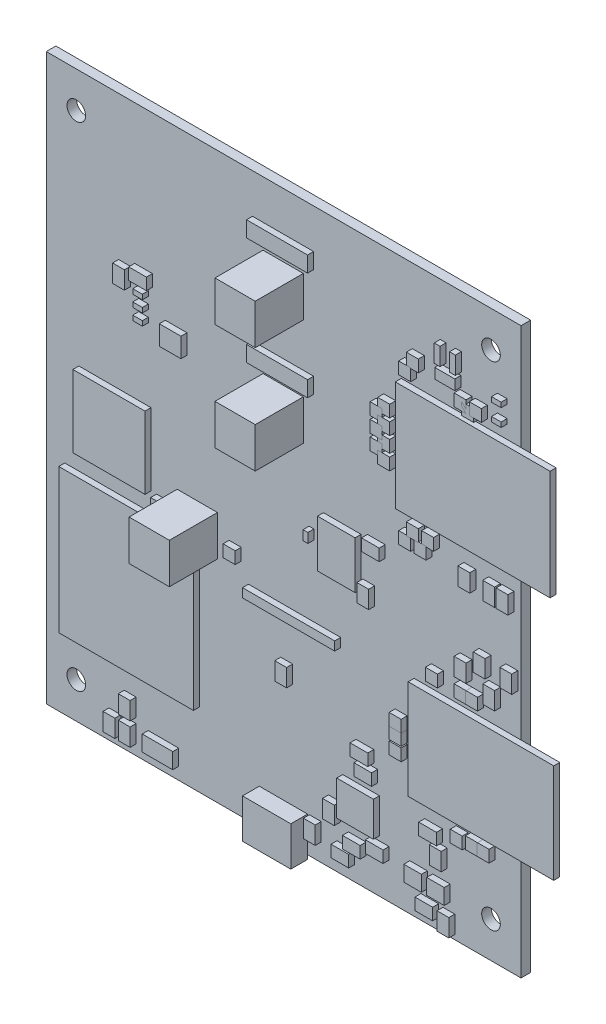
SolidWorks part; units mm, degrees
ref_plane "Front Plane" through (0, 0, 0) normal (0, 0, 1) x (1, 0, 0)
ref_plane "Top Plane" through (0, 0, 0) normal (0, 1, 0) x (1, 0, 0)
ref_plane "Right Plane" through (0, 0, 0) normal (1, 0, 0) x (0, 0, -1)
sketch "Sketch1" plane through (0, 0, 0) normal (0, 0, 1) x (1, 0, 0)
  line L0 (0, 0) -> (79, 0)
  line L1 (79, 0) -> (79, 94)
  line L2 (79, 94) -> (0, 94)
  line L3 (0, 94) -> (0, 0)
extrude "BOARD" add sketch "Sketch1" along normal blind 1.6 separate body
ref_plane "Plane1" through (0, 0, 1.6) normal (0, 0, 1) x (1, 0, 0)
sketch "Sketch2" plane through (0, 0, 1.6) normal (0, 0, 1) x (1, 0, 0)
  line L0 (25.4896, 36.2575) -> (25.4895, 12.2959)
  line L1 (25.4895, 12.2959) -> (3.0854, 12.2959)
  line L2 (3.0854, 12.2959) -> (3.0855, 36.2575)
  line L3 (3.0855, 36.2575) -> (25.4896, 36.2575)
extrude "BATTCOM_20MM_PTH_KIT-1" add sketch "Sketch2" along normal blind 1 separate body
sketch "Sketch3" plane through (0, 0, 0) normal (0, 0, 1) x (1, 0, 0)
  line L0 (38.9, 43.5808) -> (37.3, 43.5808)
  line L1 (37.3, 43.5808) -> (37.3, 42.78)
  line L2 (37.3, 42.78) -> (38.9, 42.78)
  line L3 (38.9, 42.78) -> (38.9, 43.5808)
extrude "C0603K-1" add sketch "Sketch3" against normal blind 1 separate body
sketch "Sketch4" plane through (0, 0, 0) normal (0, 0, 1) x (1, 0, 0)
  line L0 (35.3258, 23.965) -> (35.3258, 25.565)
  line L1 (35.3258, 25.565) -> (34.525, 25.565)
  line L2 (34.525, 25.565) -> (34.525, 23.965)
  line L3 (34.525, 23.965) -> (35.3258, 23.965)
extrude "C0603K-2" add sketch "Sketch4" against normal blind 1 separate body
sketch "Sketch5" plane through (0, 0, 0) normal (0, 0, 1) x (1, 0, 0)
  line L0 (37.5483, 23.965) -> (37.5483, 25.565)
  line L1 (37.5483, 25.565) -> (36.7475, 25.565)
  line L2 (36.7475, 25.565) -> (36.7475, 23.965)
  line L3 (36.7475, 23.965) -> (37.5483, 23.965)
extrude "C0603K-3" add sketch "Sketch5" against normal blind 1 separate body
sketch "Sketch6" plane through (0, 0, 0) normal (0, 0, 1) x (1, 0, 0)
  line L0 (40.0883, 23.965) -> (40.0883, 25.565)
  line L1 (40.0883, 25.565) -> (39.2875, 25.565)
  line L2 (39.2875, 25.565) -> (39.2875, 23.965)
  line L3 (39.2875, 23.965) -> (40.0883, 23.965)
extrude "C0603K-4" add sketch "Sketch6" against normal blind 1 separate body
sketch "Sketch7" plane through (0, 0, 0) normal (0, 0, 1) x (1, 0, 0)
  line L0 (42.3108, 23.965) -> (42.3108, 25.565)
  line L1 (42.3108, 25.565) -> (41.51, 25.565)
  line L2 (41.51, 25.565) -> (41.51, 23.965)
  line L3 (41.51, 23.965) -> (42.3108, 23.965)
extrude "C0603K-5" add sketch "Sketch7" against normal blind 1 separate body
sketch "Sketch8" plane through (0, 0, 0) normal (0, 0, 1) x (1, 0, 0)
  line L0 (38.57, 88.4992) -> (40.17, 88.4992)
  line L1 (40.17, 88.4992) -> (40.17, 89.3)
  line L2 (40.17, 89.3) -> (38.57, 89.3)
  line L3 (38.57, 89.3) -> (38.57, 88.4992)
extrude "C0603K-6" add sketch "Sketch8" against normal blind 1 separate body
sketch "Sketch9" plane through (0, 0, 0) normal (0, 0, 1) x (1, 0, 0)
  line L0 (28.423, 9.0045) -> (28.423, 11.9505)
  line L1 (28.423, 11.9505) -> (27.457, 11.9505)
  line L2 (27.457, 11.9505) -> (27.457, 9.0045)
  line L3 (27.457, 9.0045) -> (28.423, 9.0045)
extrude "C0402-1" add sketch "Sketch9" against normal blind 1 separate body
sketch "Sketch10" plane through (0, 0, 0) normal (0, 0, 1) x (1, 0, 0)
  line L0 (27.457, 20.2055) -> (27.457, 17.2595)
  line L1 (27.457, 17.2595) -> (28.423, 17.2595)
  line L2 (28.423, 17.2595) -> (28.423, 20.2055)
  line L3 (28.423, 20.2055) -> (27.457, 20.2055)
extrude "C0402-2" add sketch "Sketch10" against normal blind 1 separate body
sketch "Sketch11" plane through (0, 0, 0) normal (0, 0, 1) x (1, 0, 0)
  line L0 (38.57, 71.0367) -> (40.17, 71.0367)
  line L1 (40.17, 71.0367) -> (40.17, 71.8375)
  line L2 (40.17, 71.8375) -> (38.57, 71.8375)
  line L3 (38.57, 71.8375) -> (38.57, 71.0367)
extrude "C0603K-7" add sketch "Sketch11" against normal blind 1 separate body
sketch "Sketch12" plane through (0, 0, 0) normal (0, 0, 1) x (1, 0, 0)
  line L0 (18.9667, 23.3425) -> (18.9667, 21.7425)
  line L1 (18.9667, 21.7425) -> (19.7675, 21.7425)
  line L2 (19.7675, 21.7425) -> (19.7675, 23.3425)
  line L3 (19.7675, 23.3425) -> (18.9667, 23.3425)
extrude "C0603K-8" add sketch "Sketch12" against normal blind 1 separate body
sketch "Sketch13" plane through (0, 0, 0) normal (0, 0, 1) x (1, 0, 0)
  line L0 (65.0042, 30.3275) -> (65.0042, 28.7275)
  line L1 (65.0042, 28.7275) -> (65.805, 28.7275)
  line L2 (65.805, 28.7275) -> (65.805, 30.3275)
  line L3 (65.805, 30.3275) -> (65.0042, 30.3275)
extrude "C0603K-9" add sketch "Sketch13" against normal blind 1 separate body
sketch "Sketch14" plane through (0, 0, 0) normal (0, 0, 1) x (1, 0, 0)
  line L0 (66.9092, 30.3275) -> (66.9092, 28.7275)
  line L1 (66.9092, 28.7275) -> (67.71, 28.7275)
  line L2 (67.71, 28.7275) -> (67.71, 30.3275)
  line L3 (67.71, 30.3275) -> (66.9092, 30.3275)
extrude "C0603K-10" add sketch "Sketch14" against normal blind 1 separate body
sketch "Sketch15" plane through (0, 0, 0) normal (0, 0, 1) x (1, 0, 0)
  line L0 (43.3325, 12.9342) -> (44.9325, 12.9342)
  line L1 (44.9325, 12.9342) -> (44.9325, 13.735)
  line L2 (44.9325, 13.735) -> (43.3325, 13.735)
  line L3 (43.3325, 13.735) -> (43.3325, 12.9342)
extrude "C0603K-11" add sketch "Sketch15" against normal blind 1 separate body
sketch "Sketch16" plane through (0, 0, 1.6) normal (0, 0, 1) x (1, 0, 0)
  line L0 (42.7716, 58.93) -> (36.07, 58.93)
  line L1 (36.07, 58.93) -> (36.07, 65.6316)
  line L2 (36.07, 65.6316) -> (42.7716, 65.6316)
  line L3 (42.7716, 65.6316) -> (42.7716, 58.93)
extrude "153CLV-0605-1" add sketch "Sketch16" along normal blind 8 separate body
sketch "Sketch17" plane through (0, 0, 1.6) normal (0, 0, 1) x (1, 0, 0)
  line L0 (42.7716, 76.71) -> (36.07, 76.71)
  line L1 (36.07, 76.71) -> (36.07, 83.4116)
  line L2 (36.07, 83.4116) -> (42.7716, 83.4116)
  line L3 (42.7716, 83.4116) -> (42.7716, 76.71)
extrude "153CLV-0605-2" add sketch "Sketch17" along normal blind 8 separate body
sketch "Sketch18" plane through (0, 0, 0) normal (0, 0, 1) x (1, 0, 0)
  line L0 (67.7925, 22.3083) -> (66.1925, 22.3083)
  line L1 (66.1925, 22.3083) -> (66.1925, 21.5075)
  line L2 (66.1925, 21.5075) -> (67.7925, 21.5075)
  line L3 (67.7925, 21.5075) -> (67.7925, 22.3083)
extrude "C0603K-12" add sketch "Sketch18" against normal blind 1 separate body
sketch "Sketch19" plane through (0, 0, 1.6) normal (0, 0, 1) x (1, 0, 0)
  line L0 (43.7317, 45.8725) -> (43.7317, 47.4725)
  line L1 (43.7317, 47.4725) -> (44.5325, 47.4725)
  line L2 (44.5325, 47.4725) -> (44.5325, 45.8725)
  line L3 (44.5325, 45.8725) -> (43.7317, 45.8725)
extrude "C0603K-13" add sketch "Sketch19" along normal blind 1 separate body
sketch "Sketch20" plane through (0, 0, 0) normal (0, 0, 1) x (1, 0, 0)
  line L0 (6.1158, 54.445) -> (6.1158, 56.045)
  line L1 (6.1158, 56.045) -> (5.315, 56.045)
  line L2 (5.315, 56.045) -> (5.315, 54.445)
  line L3 (5.315, 54.445) -> (6.1158, 54.445)
extrude "C0603K-14" add sketch "Sketch20" against normal blind 1 separate body
sketch "Sketch21" plane through (0, 0, 0) normal (0, 0, 1) x (1, 0, 0)
  line L0 (7.785, 58.5033) -> (6.185, 58.5033)
  line L1 (6.185, 58.5033) -> (6.185, 57.7025)
  line L2 (6.185, 57.7025) -> (7.785, 57.7025)
  line L3 (7.785, 57.7025) -> (7.785, 58.5033)
extrude "C0603K-15" add sketch "Sketch21" against normal blind 1 separate body
sketch "Sketch22" plane through (0, 0, 0) normal (0, 0, 1) x (1, 0, 0)
  line L0 (15.0058, 52.54) -> (15.0058, 54.14)
  line L1 (15.0058, 54.14) -> (14.205, 54.14)
  line L2 (14.205, 54.14) -> (14.205, 52.54)
  line L3 (14.205, 52.54) -> (15.0058, 52.54)
extrude "C0603K-16" add sketch "Sketch22" against normal blind 1 separate body
sketch "Sketch23" plane through (0, 0, 0) normal (0, 0, 1) x (1, 0, 0)
  line L0 (24.2825, 39.2867) -> (25.8825, 39.2867)
  line L1 (25.8825, 39.2867) -> (25.8825, 40.0875)
  line L2 (25.8825, 40.0875) -> (24.2825, 40.0875)
  line L3 (24.2825, 40.0875) -> (24.2825, 39.2867)
extrude "C0603K-17" add sketch "Sketch23" against normal blind 1 separate body
sketch "Sketch24" plane through (0, 0, 0) normal (0, 0, 1) x (1, 0, 0)
  line L0 (27.8567, 43.0275) -> (27.8567, 41.4275)
  line L1 (27.8567, 41.4275) -> (28.6575, 41.4275)
  line L2 (28.6575, 41.4275) -> (28.6575, 43.0275)
  line L3 (28.6575, 43.0275) -> (27.8567, 43.0275)
extrude "C0603K-18" add sketch "Sketch24" against normal blind 1 separate body
sketch "Sketch25" plane through (0, 0, 1.6) normal (0, 0, 1) x (1, 0, 0)
  line L0 (28.4841, 35.1175) -> (21.7825, 35.1175)
  line L1 (21.7825, 35.1175) -> (21.7825, 41.8191)
  line L2 (21.7825, 41.8191) -> (28.4841, 41.8191)
  line L3 (28.4841, 41.8191) -> (28.4841, 35.1175)
extrude "153CLV-0605-3" add sketch "Sketch25" along normal blind 8 separate body
sketch "Sketch26" plane through (0, 0, 1.6) normal (0, 0, 1) x (1, 0, 0)
  line L0 (75.0825, 79.4583) -> (76.6825, 79.4583)
  line L1 (76.6825, 79.4583) -> (76.6825, 78.6575)
  line L2 (76.6825, 78.6575) -> (75.0825, 78.6575)
  line L3 (75.0825, 78.6575) -> (75.0825, 79.4583)
extrude "C0603K-19" add sketch "Sketch26" along normal blind 1 separate body
sketch "Sketch27" plane through (0, 0, 1.6) normal (0, 0, 1) x (1, 0, 0)
  line L0 (75.0825, 82.3158) -> (76.6825, 82.3158)
  line L1 (76.6825, 82.3158) -> (76.6825, 81.515)
  line L2 (76.6825, 81.515) -> (75.0825, 81.515)
  line L3 (75.0825, 81.515) -> (75.0825, 82.3158)
extrude "C0603K-20" add sketch "Sketch27" along normal blind 1 separate body
sketch "Sketch28" plane through (0, 0, 1.6) normal (0, 0, 1) x (1, 0, 0)
  line L0 (16.9925, 63.4167) -> (15.3925, 63.4167)
  line L1 (15.3925, 63.4167) -> (15.3925, 64.2175)
  line L2 (15.3925, 64.2175) -> (16.9925, 64.2175)
  line L3 (16.9925, 64.2175) -> (16.9925, 63.4167)
extrude "C0603K-21" add sketch "Sketch28" along normal blind 1 separate body
sketch "Sketch29" plane through (0, 0, 1.6) normal (0, 0, 1) x (1, 0, 0)
  line L0 (16.9925, 65.3217) -> (15.3925, 65.3217)
  line L1 (15.3925, 65.3217) -> (15.3925, 66.1225)
  line L2 (15.3925, 66.1225) -> (16.9925, 66.1225)
  line L3 (16.9925, 66.1225) -> (16.9925, 65.3217)
extrude "C0603K-22" add sketch "Sketch29" along normal blind 1 separate body
sketch "Sketch30" plane through (0, 0, 1.6) normal (0, 0, 1) x (1, 0, 0)
  line L0 (16.9925, 67.2267) -> (15.3925, 67.2267)
  line L1 (15.3925, 67.2267) -> (15.3925, 68.0275)
  line L2 (15.3925, 68.0275) -> (16.9925, 68.0275)
  line L3 (16.9925, 68.0275) -> (16.9925, 67.2267)
extrude "C0603K-23" add sketch "Sketch30" along normal blind 1 separate body
sketch "Sketch31" plane through (0, 0, 1.6) normal (0, 0, 1) x (1, 0, 0)
  line L0 (65.557, 82.347) -> (65.557, 85.293)
  line L1 (65.557, 85.293) -> (66.523, 85.293)
  line L2 (66.523, 85.293) -> (66.523, 82.347)
  line L3 (66.523, 82.347) -> (65.557, 82.347)
extrude "C0402-3" add sketch "Sketch31" along normal blind 1 separate body
sketch "Sketch32" plane through (0, 0, 1.6) normal (0, 0, 1) x (1, 0, 0)
  line L0 (68.097, 82.347) -> (68.097, 85.293)
  line L1 (68.097, 85.293) -> (69.063, 85.293)
  line L2 (69.063, 85.293) -> (69.063, 82.347)
  line L3 (69.063, 82.347) -> (68.097, 82.347)
extrude "C0402-4" add sketch "Sketch32" along normal blind 1 separate body
sketch "Sketch33" plane through (0, 0, 0) normal (0, 0, 1) x (1, 0, 0)
  line L0 (66.4408, 24.2825) -> (66.4408, 25.8825)
  line L1 (66.4408, 25.8825) -> (65.64, 25.8825)
  line L2 (65.64, 25.8825) -> (65.64, 24.2825)
  line L3 (65.64, 24.2825) -> (66.4408, 24.2825)
extrude "C0603K-24" add sketch "Sketch33" against normal blind 1 separate body
sketch "Sketch34" plane through (0, 0, 0) normal (0, 0, 1) x (1, 0, 0)
  line L0 (42.4307, 50.0507) -> (36.8065, 50.0507)
  line L1 (36.8065, 50.0507) -> (36.8065, 44.3738)
  line L2 (36.8065, 44.3738) -> (42.4307, 44.3738)
  line L3 (42.4307, 44.3738) -> (42.4307, 50.0507)
extrude "WS2812B-1" add sketch "Sketch34" against normal blind 1 separate body
sketch "Sketch35" plane through (0, 0, 0) normal (0, 0, 1) x (1, 0, 0)
  line L0 (40.7924, 41.6179) -> (37.8714, 41.6179)
  line L1 (37.8714, 41.6179) -> (37.8714, 39.0271)
  line L2 (37.8714, 39.0271) -> (40.7924, 39.0271)
  line L3 (40.7924, 39.0271) -> (40.7924, 41.6179)
extrude "SOT23-1" add sketch "Sketch35" against normal blind 1 separate body
sketch "Sketch36" plane through (0, 0, 0) normal (0, 0, 1) x (1, 0, 0)
  line L0 (45.5676, 21.5646) -> (48.4886, 21.5646)
  line L1 (48.4886, 21.5646) -> (48.4886, 24.1554)
  line L2 (48.4886, 24.1554) -> (45.5676, 24.1554)
  line L3 (45.5676, 24.1554) -> (45.5676, 21.5646)
extrude "SOT23-2" add sketch "Sketch36" against normal blind 1 separate body
sketch "Sketch37" plane through (0, 0, 1.6) normal (0, 0, 1) x (1, 0, 0)
  line L0 (49.3332, 14.4843) -> (55.4375, 14.4843)
  line L1 (55.4375, 14.4843) -> (55.4375, 8.705)
  line L2 (55.4375, 8.705) -> (49.3332, 8.705)
  line L3 (49.3332, 8.705) -> (49.3332, 14.4843)
extrude "MLP28-1" add sketch "Sketch37" along normal blind 1 separate body
sketch "Sketch38" plane through (0, 0, 0) normal (0, 0, 1) x (1, 0, 0)
  line L0 (12.53, 52.1384) -> (12.53, 54.5416)
  line L1 (12.53, 54.5416) -> (10.33, 54.5416)
  line L2 (10.33, 54.5416) -> (10.33, 52.1384)
  line L3 (10.33, 52.1384) -> (12.53, 52.1384)
extrude "SC70-5L-1" add sketch "Sketch38" against normal blind 1 separate body
sketch "Sketch39" plane through (0, 0, 1.6) normal (0, 0, 1) x (1, 0, 0)
  line L0 (48.9966, 32.6009) -> (33.655, 32.6009)
  line L1 (33.655, 32.6009) -> (33.655, 34.0741)
  line L2 (33.655, 34.0741) -> (48.9966, 34.0741)
  line L3 (48.9966, 34.0741) -> (48.9966, 32.6009)
extrude "1X06_LONGPADS-1" add sketch "Sketch39" along normal blind 1 separate body
sketch "Sketch40" plane through (0, 0, 1.6) normal (0, 0, 1) x (1, 0, 0)
  line L0 (35.4484, 5.8633) -> (43.4884, 5.8633)
  line L1 (43.4884, 5.8633) -> (43.4884, -0.6707)
  line L2 (43.4884, -0.6707) -> (35.4484, -0.6707)
  line L3 (35.4484, -0.6707) -> (35.4484, 5.8633)
extrude "USB-MICROB-PTH-MILL-1" add sketch "Sketch40" along normal blind 2.8 separate body
sketch "Sketch41" plane through (0, 0, 0) normal (0, 0, 1) x (1, 0, 0)
  line L0 (19.1291, 44.7259) -> (19.1291, 39.7291)
  line L1 (19.1291, 39.7291) -> (22.1205, 39.7291)
  line L2 (22.1205, 39.7291) -> (22.1205, 44.7259)
  line L3 (22.1205, 44.7259) -> (19.1291, 44.7259)
extrude "L3225M-1" add sketch "Sketch41" against normal blind 1 separate body
sketch "Sketch42" plane through (0, 0, 1.6) normal (0, 0, 1) x (1, 0, 0)
  line L0 (34.3237, 69.4585) -> (44.4837, 69.4585)
  line L1 (44.4837, 69.4585) -> (44.4837, 66.8423)
  line L2 (44.4837, 66.8423) -> (34.3237, 66.8423)
  line L3 (34.3237, 66.8423) -> (34.3237, 69.4585)
extrude "1X04-1" add sketch "Sketch42" along normal blind 1 separate body
sketch "Sketch43" plane through (0, 0, 1.6) normal (0, 0, 1) x (1, 0, 0)
  line L0 (34.3232, 87.4253) -> (44.4832, 87.4253)
  line L1 (44.4832, 87.4253) -> (44.4832, 84.8091)
  line L2 (44.4832, 84.8091) -> (34.3232, 84.8091)
  line L3 (34.3232, 84.8091) -> (34.3232, 87.4253)
extrude "1X04-2" add sketch "Sketch43" along normal blind 1 separate body
sketch "Sketch44" plane through (0, 0, 1.6) normal (0, 0, 1) x (1, 0, 0)
  line L0 (16.9625, 4.6457) -> (22.0425, 4.6457)
  line L1 (22.0425, 4.6457) -> (22.0425, 2.0295)
  line L2 (22.0425, 2.0295) -> (16.9625, 2.0295)
  line L3 (16.9625, 2.0295) -> (16.9625, 4.6457)
extrude "1X02-1" add sketch "Sketch44" along normal blind 1 separate body
sketch "Sketch45" plane through (0, 0, 1.6) normal (0, 0, 1) x (1, 0, 0)
  line L0 (5.4284, 51.4041) -> (17.4316, 51.4041)
  line L1 (17.4316, 51.4041) -> (17.4316, 39.4009)
  line L2 (17.4316, 39.4009) -> (5.4284, 39.4009)
  line L3 (5.4284, 39.4009) -> (5.4284, 51.4041)
extrude "BUZZER-12MM-NS-KIT-1" add sketch "Sketch45" along normal blind 1 separate body
sketch "Sketch46" plane through (0, 0, 1.6) normal (0, 0, 1) x (1, 0, 0)
  line L0 (66.0095, 0.7495) -> (66.0095, 3.6955)
  line L1 (66.0095, 3.6955) -> (67.9755, 3.6955)
  line L2 (67.9755, 3.6955) -> (67.9755, 0.7495)
  line L3 (67.9755, 0.7495) -> (66.0095, 0.7495)
extrude "R0603-1" add sketch "Sketch46" along normal blind 1 separate body
sketch "Sketch47" plane through (0, 0, 1.6) normal (0, 0, 1) x (1, 0, 0)
  line L0 (65.2905, 1.8745) -> (62.3445, 1.8745)
  line L1 (62.3445, 1.8745) -> (62.3445, 3.8405)
  line L2 (62.3445, 3.8405) -> (65.2905, 3.8405)
  line L3 (65.2905, 3.8405) -> (65.2905, 1.8745)
extrude "R0603-2" add sketch "Sketch47" along normal blind 1 separate body
sketch "Sketch48" plane through (0, 0, 1.6) normal (0, 0, 1) x (1, 0, 0)
  line L0 (54.4955, 18.702) -> (51.5495, 18.702)
  line L1 (51.5495, 18.702) -> (51.5495, 20.668)
  line L2 (51.5495, 20.668) -> (54.4955, 20.668)
  line L3 (54.4955, 20.668) -> (54.4955, 18.702)
extrude "R0603-3" add sketch "Sketch48" along normal blind 1 separate body
sketch "Sketch49" plane through (0, 0, 1.6) normal (0, 0, 1) x (1, 0, 0)
  line L0 (55.1305, 16.162) -> (52.1845, 16.162)
  line L1 (52.1845, 16.162) -> (52.1845, 18.128)
  line L2 (52.1845, 18.128) -> (55.1305, 18.128)
  line L3 (55.1305, 18.128) -> (55.1305, 16.162)
extrude "R0603-4" add sketch "Sketch49" along normal blind 1 separate body
sketch "Sketch50" plane through (0, 0, 0) normal (0, 0, 1) x (1, 0, 0)
  line L0 (39.802, 10.447) -> (42.748, 10.447)
  line L1 (42.748, 10.447) -> (42.748, 12.413)
  line L2 (42.748, 12.413) -> (39.802, 12.413)
  line L3 (39.802, 12.413) -> (39.802, 10.447)
extrude "R0603-5" add sketch "Sketch50" against normal blind 1 separate body
sketch "Sketch51" plane through (0, 0, 0) normal (0, 0, 1) x (1, 0, 0)
  line L0 (38.6205, 12.413) -> (35.6745, 12.413)
  line L1 (35.6745, 12.413) -> (35.6745, 10.447)
  line L2 (35.6745, 10.447) -> (38.6205, 10.447)
  line L3 (38.6205, 10.447) -> (38.6205, 12.413)
extrude "R0603-6" add sketch "Sketch51" against normal blind 1 separate body
sketch "Sketch52" plane through (0, 0, 0) normal (0, 0, 1) x (1, 0, 0)
  line L0 (46.4695, 16.162) -> (49.4155, 16.162)
  line L1 (49.4155, 16.162) -> (49.4155, 18.128)
  line L2 (49.4155, 18.128) -> (46.4695, 18.128)
  line L3 (46.4695, 18.128) -> (46.4695, 16.162)
extrude "R0603-7" add sketch "Sketch52" against normal blind 1 separate body
sketch "Sketch53" plane through (0, 0, 0) normal (0, 0, 1) x (1, 0, 0)
  line L0 (41.3055, 10.9095) -> (41.3055, 13.8555)
  line L1 (41.3055, 13.8555) -> (39.3395, 13.8555)
  line L2 (39.3395, 13.8555) -> (39.3395, 10.9095)
  line L3 (39.3395, 10.9095) -> (41.3055, 10.9095)
extrude "R0603-8" add sketch "Sketch53" against normal blind 1 separate body
sketch "Sketch54" plane through (0, 0, 0) normal (0, 0, 1) x (1, 0, 0)
  line L0 (39.083, 10.9095) -> (39.083, 13.8555)
  line L1 (39.083, 13.8555) -> (37.117, 13.8555)
  line L2 (37.117, 13.8555) -> (37.117, 10.9095)
  line L3 (37.117, 10.9095) -> (39.083, 10.9095)
extrude "R0603-9" add sketch "Sketch54" against normal blind 1 separate body
sketch "Sketch55" plane through (0, 0, 0) normal (0, 0, 1) x (1, 0, 0)
  line L0 (46.4695, 18.702) -> (49.4155, 18.702)
  line L1 (49.4155, 18.702) -> (49.4155, 20.668)
  line L2 (49.4155, 20.668) -> (46.4695, 20.668)
  line L3 (46.4695, 20.668) -> (46.4695, 18.702)
extrude "R0603-10" add sketch "Sketch55" against normal blind 1 separate body
sketch "Sketch56" plane through (0, 0, 1.6) normal (0, 0, 1) x (1, 0, 0)
  line L0 (40.988, 26.238) -> (40.988, 23.292)
  line L1 (40.988, 23.292) -> (39.022, 23.292)
  line L2 (39.022, 23.292) -> (39.022, 26.238)
  line L3 (39.022, 26.238) -> (40.988, 26.238)
extrude "R0603-11" add sketch "Sketch56" along normal blind 1 separate body
sketch "Sketch57" plane through (0, 0, 0) normal (0, 0, 1) x (1, 0, 0)
  line L0 (77.818, 21.387) -> (77.818, 24.333)
  line L1 (77.818, 24.333) -> (75.852, 24.333)
  line L2 (75.852, 24.333) -> (75.852, 21.387)
  line L3 (75.852, 21.387) -> (77.818, 21.387)
extrude "R0603-12" add sketch "Sketch57" against normal blind 1 separate body
sketch "Sketch58" plane through (0, 0, 0) normal (0, 0, 1) x (1, 0, 0)
  line L0 (75.278, 21.387) -> (75.278, 24.333)
  line L1 (75.278, 24.333) -> (73.312, 24.333)
  line L2 (73.312, 24.333) -> (73.312, 21.387)
  line L3 (73.312, 21.387) -> (75.278, 21.387)
extrude "R0603-13" add sketch "Sketch58" against normal blind 1 separate body
sketch "Sketch59" plane through (0, 0, 1.6) normal (0, 0, 1) x (1, 0, 0)
  line L0 (75.5955, 40.208) -> (75.5955, 37.262)
  line L1 (75.5955, 37.262) -> (73.6295, 37.262)
  line L2 (73.6295, 37.262) -> (73.6295, 40.208)
  line L3 (73.6295, 40.208) -> (75.5955, 40.208)
extrude "R0603-14" add sketch "Sketch59" along normal blind 1 separate body
sketch "Sketch60" plane through (0, 0, 0) normal (0, 0, 1) x (1, 0, 0)
  line L0 (69.2455, 23.6095) -> (69.2455, 26.5555)
  line L1 (69.2455, 26.5555) -> (67.2795, 26.5555)
  line L2 (67.2795, 26.5555) -> (67.2795, 23.6095)
  line L3 (67.2795, 23.6095) -> (69.2455, 23.6095)
extrude "R0603-15" add sketch "Sketch60" against normal blind 1 separate body
sketch "Sketch61" plane through (0, 0, 0) normal (0, 0, 1) x (1, 0, 0)
  line L0 (14.7195, 27.2745) -> (17.6655, 27.2745)
  line L1 (17.6655, 27.2745) -> (17.6655, 29.2405)
  line L2 (17.6655, 29.2405) -> (14.7195, 29.2405)
  line L3 (14.7195, 29.2405) -> (14.7195, 27.2745)
extrude "R0603-16" add sketch "Sketch61" against normal blind 1 separate body
sketch "Sketch62" plane through (0, 0, 1.6) normal (0, 0, 1) x (1, 0, 0)
  line L0 (56.4005, 49.182) -> (53.4545, 49.182)
  line L1 (53.4545, 49.182) -> (53.4545, 51.148)
  line L2 (53.4545, 51.148) -> (56.4005, 51.148)
  line L3 (56.4005, 51.148) -> (56.4005, 49.182)
extrude "R0603-17" add sketch "Sketch62" along normal blind 1 separate body
sketch "Sketch63" plane through (0, 0, 1.6) normal (0, 0, 1) x (1, 0, 0)
  line L0 (12.413, 4.648) -> (12.413, 1.702)
  line L1 (12.413, 1.702) -> (10.447, 1.702)
  line L2 (10.447, 1.702) -> (10.447, 4.648)
  line L3 (10.447, 4.648) -> (12.413, 4.648)
extrude "R0603-18" add sketch "Sketch63" along normal blind 1 separate body
sketch "Sketch64" plane through (0, 0, 1.6) normal (0, 0, 1) x (1, 0, 0)
  line L0 (14.953, 8.458) -> (14.953, 5.512)
  line L1 (14.953, 5.512) -> (12.987, 5.512)
  line L2 (12.987, 5.512) -> (12.987, 8.458)
  line L3 (12.987, 8.458) -> (14.953, 8.458)
extrude "R0603-19" add sketch "Sketch64" along normal blind 1 separate body
sketch "Sketch65" plane through (0, 0, 1.6) normal (0, 0, 1) x (1, 0, 0)
  line L0 (14.953, 4.648) -> (14.953, 1.702)
  line L1 (14.953, 1.702) -> (12.987, 1.702)
  line L2 (12.987, 1.702) -> (12.987, 4.648)
  line L3 (12.987, 4.648) -> (14.953, 4.648)
extrude "R0603-20" add sketch "Sketch65" along normal blind 1 separate body
sketch "Sketch66" plane through (0, 0, 1.6) normal (0, 0, 1) x (1, 0, 0)
  line L0 (45.7505, 5.918) -> (45.7505, 2.972)
  line L1 (45.7505, 2.972) -> (43.7845, 2.972)
  line L2 (43.7845, 2.972) -> (43.7845, 5.918)
  line L3 (43.7845, 5.918) -> (45.7505, 5.918)
extrude "R0603-21" add sketch "Sketch66" along normal blind 1 separate body
sketch "Sketch67" plane through (0, 0, 0) normal (0, 0, 1) x (1, 0, 0)
  line L0 (37.4955, 38.532) -> (37.4955, 41.478)
  line L1 (37.4955, 41.478) -> (35.5295, 41.478)
  line L2 (35.5295, 41.478) -> (35.5295, 38.532)
  line L3 (35.5295, 38.532) -> (37.4955, 38.532)
extrude "R0603-22" add sketch "Sketch67" against normal blind 1 separate body
sketch "Sketch68" plane through (0, 0, 0) normal (0, 0, 1) x (1, 0, 0)
  line L0 (35.847, 53.2255) -> (35.847, 50.2795)
  line L1 (35.847, 50.2795) -> (37.813, 50.2795)
  line L2 (37.813, 50.2795) -> (37.813, 53.2255)
  line L3 (37.813, 53.2255) -> (35.847, 53.2255)
extrude "R0603-23" add sketch "Sketch68" against normal blind 1 separate body
sketch "Sketch69" plane through (0, 0, 0) normal (0, 0, 1) x (1, 0, 0)
  line L0 (40.353, 74.727) -> (40.353, 77.673)
  line L1 (40.353, 77.673) -> (38.387, 77.673)
  line L2 (38.387, 77.673) -> (38.387, 74.727)
  line L3 (38.387, 74.727) -> (40.353, 74.727)
extrude "R0603-24" add sketch "Sketch69" against normal blind 1 separate body
sketch "Sketch70" plane through (0, 0, 1.6) normal (0, 0, 1) x (1, 0, 0)
  line L0 (76.487, 41.072) -> (76.487, 44.018)
  line L1 (76.487, 44.018) -> (78.453, 44.018)
  line L2 (78.453, 44.018) -> (78.453, 41.072)
  line L3 (78.453, 41.072) -> (76.487, 41.072)
extrude "R0603-25" add sketch "Sketch70" along normal blind 1 separate body
sketch "Sketch71" plane through (0, 0, 1.6) normal (0, 0, 1) x (1, 0, 0)
  line L0 (72.042, 41.072) -> (72.042, 44.018)
  line L1 (72.042, 44.018) -> (74.008, 44.018)
  line L2 (74.008, 44.018) -> (74.008, 41.072)
  line L3 (74.008, 41.072) -> (72.042, 41.072)
extrude "R0603-26" add sketch "Sketch71" along normal blind 1 separate body
sketch "Sketch72" plane through (0, 0, 0) normal (0, 0, 1) x (1, 0, 0)
  line L0 (74.1805, 28.6055) -> (71.2345, 28.6055)
  line L1 (71.2345, 28.6055) -> (71.2345, 26.6395)
  line L2 (71.2345, 26.6395) -> (74.1805, 26.6395)
  line L3 (74.1805, 26.6395) -> (74.1805, 28.6055)
extrude "R0603-27" add sketch "Sketch72" against normal blind 1 separate body
sketch "Sketch73" plane through (0, 0, 0) normal (0, 0, 1) x (1, 0, 0)
  line L0 (66.7895, 32.037) -> (69.7355, 32.037)
  line L1 (69.7355, 32.037) -> (69.7355, 34.003)
  line L2 (69.7355, 34.003) -> (66.7895, 34.003)
  line L3 (66.7895, 34.003) -> (66.7895, 32.037)
extrude "R0603-28" add sketch "Sketch73" against normal blind 1 separate body
sketch "Sketch74" plane through (0, 0, 0) normal (0, 0, 1) x (1, 0, 0)
  line L0 (74.1805, 31.1455) -> (71.2345, 31.1455)
  line L1 (71.2345, 31.1455) -> (71.2345, 29.1795)
  line L2 (71.2345, 29.1795) -> (74.1805, 29.1795)
  line L3 (74.1805, 29.1795) -> (74.1805, 31.1455)
extrude "R0603-29" add sketch "Sketch74" against normal blind 1 separate body
sketch "Sketch75" plane through (0, 0, 1.6) normal (0, 0, 1) x (1, 0, 0)
  line L0 (65.9255, 12.987) -> (62.9795, 12.987)
  line L1 (62.9795, 12.987) -> (62.9795, 14.953)
  line L2 (62.9795, 14.953) -> (65.9255, 14.953)
  line L3 (65.9255, 14.953) -> (65.9255, 12.987)
extrude "R0603-30" add sketch "Sketch75" along normal blind 1 separate body
sketch "Sketch76" plane through (0, 0, 1.6) normal (0, 0, 1) x (1, 0, 0)
  line L0 (68.867, 38.8495) -> (68.867, 41.7955)
  line L1 (68.867, 41.7955) -> (70.833, 41.7955)
  line L2 (70.833, 41.7955) -> (70.833, 38.8495)
  line L3 (70.833, 38.8495) -> (68.867, 38.8495)
extrude "R0603-31" add sketch "Sketch76" along normal blind 1 separate body
sketch "Sketch77" plane through (0, 0, 0) normal (0, 0, 1) x (1, 0, 0)
  line L0 (12.497, 49.182) -> (15.443, 49.182)
  line L1 (15.443, 49.182) -> (15.443, 51.148)
  line L2 (15.443, 51.148) -> (12.497, 51.148)
  line L3 (12.497, 51.148) -> (12.497, 49.182)
extrude "R0603-32" add sketch "Sketch77" against normal blind 1 separate body
sketch "Sketch78" plane through (0, 0, 0) normal (0, 0, 1) x (1, 0, 0)
  line L0 (8.458, 61.6255) -> (5.512, 61.6255)
  line L1 (5.512, 61.6255) -> (5.512, 59.6595)
  line L2 (5.512, 59.6595) -> (8.458, 59.6595)
  line L3 (8.458, 59.6595) -> (8.458, 61.6255)
extrude "R0603-33" add sketch "Sketch78" against normal blind 1 separate body
sketch "Sketch79" plane through (0, 0, 0) normal (0, 0, 1) x (1, 0, 0)
  line L0 (11.778, 48.692) -> (11.778, 51.638)
  line L1 (11.778, 51.638) -> (9.812, 51.638)
  line L2 (9.812, 51.638) -> (9.812, 48.692)
  line L3 (9.812, 48.692) -> (11.778, 48.692)
extrude "R0603-34" add sketch "Sketch79" against normal blind 1 separate body
sketch "Sketch80" plane through (0, 0, 0) normal (0, 0, 1) x (1, 0, 0)
  line L0 (7.272, 53.543) -> (7.272, 50.597)
  line L1 (7.272, 50.597) -> (9.238, 50.597)
  line L2 (9.238, 50.597) -> (9.238, 53.543)
  line L3 (9.238, 53.543) -> (7.272, 53.543)
extrude "R0603-35" add sketch "Sketch80" against normal blind 1 separate body
sketch "Sketch81" plane through (0, 0, 0) normal (0, 0, 1) x (1, 0, 0)
  line L0 (12.903, 56.863) -> (9.957, 56.863)
  line L1 (9.957, 56.863) -> (9.957, 54.897)
  line L2 (9.957, 54.897) -> (12.903, 54.897)
  line L3 (12.903, 54.897) -> (12.903, 56.863)
extrude "R0603-36" add sketch "Sketch81" against normal blind 1 separate body
sketch "Sketch82" plane through (0, 0, 0) normal (0, 0, 1) x (1, 0, 0)
  line L0 (9.238, 53.772) -> (9.238, 56.718)
  line L1 (9.238, 56.718) -> (7.272, 56.718)
  line L2 (7.272, 56.718) -> (7.272, 53.772)
  line L3 (7.272, 53.772) -> (9.238, 53.772)
extrude "R0603-37" add sketch "Sketch82" against normal blind 1 separate body
sketch "Sketch83" plane through (0, 0, 0) normal (0, 0, 1) x (1, 0, 0)
  line L0 (7.272, 41.7955) -> (7.272, 38.8495)
  line L1 (7.272, 38.8495) -> (9.238, 38.8495)
  line L2 (9.238, 38.8495) -> (9.238, 41.7955)
  line L3 (9.238, 41.7955) -> (7.272, 41.7955)
extrude "R0603-38" add sketch "Sketch83" against normal blind 1 separate body
sketch "Sketch84" plane through (0, 0, 0) normal (0, 0, 1) x (1, 0, 0)
  line L0 (10.363, 37.4955) -> (7.417, 37.4955)
  line L1 (7.417, 37.4955) -> (7.417, 35.5295)
  line L2 (7.417, 35.5295) -> (10.363, 35.5295)
  line L3 (10.363, 35.5295) -> (10.363, 37.4955)
extrude "R0603-39" add sketch "Sketch84" against normal blind 1 separate body
sketch "Sketch85" plane through (0, 0, 1.6) normal (0, 0, 1) x (1, 0, 0)
  line L0 (57.0355, 6.002) -> (54.0895, 6.002)
  line L1 (54.0895, 6.002) -> (54.0895, 7.968)
  line L2 (54.0895, 7.968) -> (57.0355, 7.968)
  line L3 (57.0355, 7.968) -> (57.0355, 6.002)
extrude "R0603-40" add sketch "Sketch85" along normal blind 1 separate body
sketch "Sketch86" plane through (0, 0, 0) normal (0, 0, 1) x (1, 0, 0)
  line L0 (31.1455, 40.7545) -> (31.1455, 43.7005)
  line L1 (31.1455, 43.7005) -> (29.1795, 43.7005)
  line L2 (29.1795, 43.7005) -> (29.1795, 40.7545)
  line L3 (29.1795, 40.7545) -> (31.1455, 40.7545)
extrude "R0603-41" add sketch "Sketch86" against normal blind 1 separate body
sketch "Sketch87" plane through (0, 0, 1.6) normal (0, 0, 1) x (1, 0, 0)
  line L0 (48.9255, 10.363) -> (48.9255, 7.417)
  line L1 (48.9255, 7.417) -> (46.9595, 7.417)
  line L2 (46.9595, 7.417) -> (46.9595, 10.363)
  line L3 (46.9595, 10.363) -> (48.9255, 10.363)
extrude "R0603-42" add sketch "Sketch87" along normal blind 1 separate body
sketch "Sketch88" plane through (0, 0, 1.6) normal (0, 0, 1) x (1, 0, 0)
  line L0 (50.2795, 6.698) -> (53.2255, 6.698)
  line L1 (53.2255, 6.698) -> (53.2255, 4.732)
  line L2 (53.2255, 4.732) -> (50.2795, 4.732)
  line L3 (50.2795, 4.732) -> (50.2795, 6.698)
extrude "R0603-43" add sketch "Sketch88" along normal blind 1 separate body
sketch "Sketch89" plane through (0, 0, 1.6) normal (0, 0, 1) x (1, 0, 0)
  line L0 (48.3745, 4.4755) -> (51.3205, 4.4755)
  line L1 (51.3205, 4.4755) -> (51.3205, 2.5095)
  line L2 (51.3205, 2.5095) -> (48.3745, 2.5095)
  line L3 (48.3745, 2.5095) -> (48.3745, 4.4755)
extrude "R0603-44" add sketch "Sketch89" along normal blind 1 separate body
sketch "Sketch90" plane through (0, 0, 1.6) normal (0, 0, 1) x (1, 0, 0)
  line L0 (12.0345, 67.107) -> (12.0345, 70.053)
  line L1 (12.0345, 70.053) -> (14.0005, 70.053)
  line L2 (14.0005, 70.053) -> (14.0005, 67.107)
  line L3 (14.0005, 67.107) -> (12.0345, 67.107)
extrude "R0603-45" add sketch "Sketch90" along normal blind 1 separate body
sketch "Sketch91" plane through (0, 0, 1.6) normal (0, 0, 1) x (1, 0, 0)
  line L0 (14.7195, 70.833) -> (17.6655, 70.833)
  line L1 (17.6655, 70.833) -> (17.6655, 68.867)
  line L2 (17.6655, 68.867) -> (14.7195, 68.867)
  line L3 (14.7195, 68.867) -> (14.7195, 70.833)
extrude "R0603-46" add sketch "Sketch91" along normal blind 1 separate body
sketch "Sketch92" plane through (0, 0, 0) normal (0, 0, 1) x (1, 0, 0)
  line L0 (65.2905, 65.118) -> (62.3445, 65.118)
  line L1 (62.3445, 65.118) -> (62.3445, 63.152)
  line L2 (62.3445, 63.152) -> (65.2905, 63.152)
  line L3 (65.2905, 63.152) -> (65.2905, 65.118)
extrude "R0603-47" add sketch "Sketch92" against normal blind 1 separate body
sketch "Sketch93" plane through (0, 0, 0) normal (0, 0, 1) x (1, 0, 0)
  line L0 (65.2905, 62.578) -> (62.3445, 62.578)
  line L1 (62.3445, 62.578) -> (62.3445, 60.612)
  line L2 (62.3445, 60.612) -> (65.2905, 60.612)
  line L3 (65.2905, 60.612) -> (65.2905, 62.578)
extrude "R0603-48" add sketch "Sketch93" against normal blind 1 separate body
sketch "Sketch94" plane through (0, 0, 0) normal (0, 0, 1) x (1, 0, 0)
  line L0 (66.0095, 63.3855) -> (66.0095, 60.4395)
  line L1 (66.0095, 60.4395) -> (67.9755, 60.4395)
  line L2 (67.9755, 60.4395) -> (67.9755, 63.3855)
  line L3 (67.9755, 63.3855) -> (66.0095, 63.3855)
extrude "R0603-49" add sketch "Sketch94" against normal blind 1 separate body
sketch "Sketch95" plane through (0, 0, 1.6) normal (0, 0, 1) x (1, 0, 0)
  line L0 (69.502, 52.1845) -> (69.502, 55.1305)
  line L1 (69.502, 55.1305) -> (71.468, 55.1305)
  line L2 (71.468, 55.1305) -> (71.468, 52.1845)
  line L3 (71.468, 52.1845) -> (69.502, 52.1845)
extrude "R0603-50" add sketch "Sketch95" along normal blind 1 separate body
sketch "Sketch96" plane through (0, 0, 1.6) normal (0, 0, 1) x (1, 0, 0)
  line L0 (73.6295, 52.1845) -> (73.6295, 55.1305)
  line L1 (73.6295, 55.1305) -> (75.5955, 55.1305)
  line L2 (75.5955, 55.1305) -> (75.5955, 52.1845)
  line L3 (75.5955, 52.1845) -> (73.6295, 52.1845)
extrude "R0603-51" add sketch "Sketch96" along normal blind 1 separate body
sketch "Sketch97" plane through (0, 0, 1.6) normal (0, 0, 1) x (1, 0, 0)
  line L0 (75.852, 52.1845) -> (75.852, 55.1305)
  line L1 (75.852, 55.1305) -> (77.818, 55.1305)
  line L2 (77.818, 55.1305) -> (77.818, 52.1845)
  line L3 (77.818, 52.1845) -> (75.852, 52.1845)
extrude "R0603-52" add sketch "Sketch97" along normal blind 1 separate body
sketch "Sketch98" plane through (0, 0, 1.6) normal (0, 0, 1) x (1, 0, 0)
  line L0 (54.6405, 44.3355) -> (54.6405, 41.3895)
  line L1 (54.6405, 41.3895) -> (52.6745, 41.3895)
  line L2 (52.6745, 41.3895) -> (52.6745, 44.3355)
  line L3 (52.6745, 44.3355) -> (54.6405, 44.3355)
extrude "R0603-53" add sketch "Sketch98" along normal blind 1 separate body
sketch "Sketch99" plane through (0, 0, 1.6) normal (0, 0, 1) x (1, 0, 0)
  line L0 (64.7395, 9.6395) -> (64.7395, 12.5855)
  line L1 (64.7395, 12.5855) -> (66.7055, 12.5855)
  line L2 (66.7055, 12.5855) -> (66.7055, 9.6395)
  line L3 (66.7055, 9.6395) -> (64.7395, 9.6395)
extrude "R0603-54" add sketch "Sketch99" along normal blind 1 separate body
sketch "Sketch100" plane through (0, 0, 1.6) normal (0, 0, 1) x (1, 0, 0)
  line L0 (85.441, 34.29) -> (85.441, 17.78)
  line L1 (85.441, 17.78) -> (61.214, 17.78)
  line L2 (61.214, 17.78) -> (61.214, 34.29)
  line L3 (61.214, 34.29) -> (85.441, 34.29)
extrude "ESP8266-ESP12E-1" add sketch "Sketch100" along normal blind 1 separate body
sketch "Sketch101" plane through (0, 0, 1.6) normal (0, 0, 1) x (1, 0, 0)
  line L0 (64.3001, 7.6454) -> (67.2211, 7.6454)
  line L1 (67.2211, 7.6454) -> (67.2211, 5.0546)
  line L2 (67.2211, 5.0546) -> (64.3001, 5.0546)
  line L3 (64.3001, 5.0546) -> (64.3001, 7.6454)
extrude "SOT23-3" add sketch "Sketch101" along normal blind 1 separate body
sketch "Sketch102" plane through (0, 0, 1.6) normal (0, 0, 1) x (1, 0, 0)
  line L0 (60.4901, 7.6454) -> (63.4111, 7.6454)
  line L1 (63.4111, 7.6454) -> (63.4111, 5.0546)
  line L2 (63.4111, 5.0546) -> (60.4901, 5.0546)
  line L3 (60.4901, 5.0546) -> (60.4901, 7.6454)
extrude "SOT23-4" add sketch "Sketch102" along normal blind 1 separate body
sketch "Sketch103" plane through (0, 0, 0) normal (0, 0, 1) x (1, 0, 0)
  line L0 (12.2174, 41.6179) -> (9.2964, 41.6179)
  line L1 (9.2964, 41.6179) -> (9.2964, 39.0271)
  line L2 (9.2964, 39.0271) -> (12.2174, 39.0271)
  line L3 (12.2174, 39.0271) -> (12.2174, 41.6179)
extrude "SOT23-5" add sketch "Sketch103" against normal blind 1 separate body
sketch "Sketch104" plane through (0, 0, 1.6) normal (0, 0, 1) x (1, 0, 0)
  line L0 (72.755, 35.83) -> (70.755, 35.83)
  line L1 (70.755, 35.83) -> (70.755, 37.83)
  line L2 (70.755, 37.83) -> (72.755, 37.83)
  line L3 (72.755, 37.83) -> (72.755, 35.83)
extrude "TP10R-1" add sketch "Sketch104" along normal blind 1 separate body
sketch "Sketch105" plane through (0, 0, 1.6) normal (0, 0, 1) x (1, 0, 0)
  line L0 (74.66, 14.875) -> (72.66, 14.875)
  line L1 (72.66, 14.875) -> (72.66, 16.875)
  line L2 (72.66, 16.875) -> (74.66, 16.875)
  line L3 (74.66, 16.875) -> (74.66, 14.875)
extrude "TP10R-2" add sketch "Sketch105" along normal blind 1 separate body
sketch "Sketch106" plane through (0, 0, 1.6) normal (0, 0, 1) x (1, 0, 0)
  line L0 (70.85, 35.83) -> (68.85, 35.83)
  line L1 (68.85, 35.83) -> (68.85, 37.83)
  line L2 (68.85, 37.83) -> (70.85, 37.83)
  line L3 (70.85, 37.83) -> (70.85, 35.83)
extrude "TP10R-3" add sketch "Sketch106" along normal blind 1 separate body
sketch "Sketch107" plane through (0, 0, 1.6) normal (0, 0, 1) x (1, 0, 0)
  line L0 (66.0875, 35.83) -> (64.0875, 35.83)
  line L1 (64.0875, 35.83) -> (64.0875, 37.83)
  line L2 (64.0875, 37.83) -> (66.0875, 37.83)
  line L3 (66.0875, 37.83) -> (66.0875, 35.83)
extrude "TP10R-4" add sketch "Sketch107" along normal blind 1 separate body
sketch "Sketch108" plane through (0, 0, 1.6) normal (0, 0, 1) x (1, 0, 0)
  line L0 (60.055, 22.1775) -> (58.055, 22.1775)
  line L1 (58.055, 22.1775) -> (58.055, 24.1775)
  line L2 (58.055, 24.1775) -> (60.055, 24.1775)
  line L3 (60.055, 24.1775) -> (60.055, 22.1775)
extrude "TP10R-5" add sketch "Sketch108" along normal blind 1 separate body
sketch "Sketch109" plane through (0, 0, 1.6) normal (0, 0, 1) x (1, 0, 0)
  line L0 (70.215, 14.5575) -> (68.215, 14.5575)
  line L1 (68.215, 14.5575) -> (68.215, 16.5575)
  line L2 (68.215, 16.5575) -> (70.215, 16.5575)
  line L3 (70.215, 16.5575) -> (70.215, 14.5575)
extrude "TP10R-6" add sketch "Sketch109" along normal blind 1 separate body
sketch "Sketch110" plane through (0, 0, 1.6) normal (0, 0, 1) x (1, 0, 0)
  line L0 (60.055, 26.305) -> (58.055, 26.305)
  line L1 (58.055, 26.305) -> (58.055, 28.305)
  line L2 (58.055, 28.305) -> (60.055, 28.305)
  line L3 (60.055, 28.305) -> (60.055, 26.305)
extrude "TP10R-7" add sketch "Sketch110" along normal blind 1 separate body
sketch "Sketch111" plane through (0, 0, 1.6) normal (0, 0, 1) x (1, 0, 0)
  line L0 (60.055, 24.4) -> (58.055, 24.4)
  line L1 (58.055, 24.4) -> (58.055, 26.4)
  line L2 (58.055, 26.4) -> (60.055, 26.4)
  line L3 (60.055, 26.4) -> (60.055, 24.4)
extrude "TP10R-8" add sketch "Sketch111" along normal blind 1 separate body
sketch "Sketch112" plane through (0, 0, 1.6) normal (0, 0, 1) x (1, 0, 0)
  line L0 (72.755, 14.875) -> (70.755, 14.875)
  line L1 (70.755, 14.875) -> (70.755, 16.875)
  line L2 (70.755, 16.875) -> (72.755, 16.875)
  line L3 (72.755, 16.875) -> (72.755, 14.875)
extrude "TP10R-9" add sketch "Sketch112" along normal blind 1 separate body
sketch "Sketch113" plane through (0, 0, 1.6) normal (0, 0, 1) x (1, 0, 0)
  line L0 (61.6425, 77.74) -> (59.6425, 77.74)
  line L1 (59.6425, 77.74) -> (59.6425, 79.74)
  line L2 (59.6425, 79.74) -> (61.6425, 79.74)
  line L3 (61.6425, 79.74) -> (61.6425, 77.74)
extrude "TP10R-10" add sketch "Sketch113" along normal blind 1 separate body
sketch "Sketch114" plane through (0, 0, 1.6) normal (0, 0, 1) x (1, 0, 0)
  line L0 (20.3675, 37.4175) -> (18.3675, 37.4175)
  line L1 (18.3675, 37.4175) -> (18.3675, 39.4175)
  line L2 (18.3675, 39.4175) -> (20.3675, 39.4175)
  line L3 (20.3675, 39.4175) -> (20.3675, 37.4175)
extrude "TP10R-11" add sketch "Sketch114" along normal blind 1 separate body
sketch "Sketch115" plane through (0, 0, 1.6) normal (0, 0, 1) x (1, 0, 0)
  line L0 (58.15, 70.755) -> (56.15, 70.755)
  line L1 (56.15, 70.755) -> (56.15, 72.755)
  line L2 (56.15, 72.755) -> (58.15, 72.755)
  line L3 (58.15, 72.755) -> (58.15, 70.755)
extrude "TP10R-12" add sketch "Sketch115" along normal blind 1 separate body
sketch "Sketch116" plane through (0, 0, 1.6) normal (0, 0, 1) x (1, 0, 0)
  line L0 (32.4325, 36.7825) -> (30.4325, 36.7825)
  line L1 (30.4325, 36.7825) -> (30.4325, 38.7825)
  line L2 (30.4325, 38.7825) -> (32.4325, 38.7825)
  line L3 (32.4325, 38.7825) -> (32.4325, 36.7825)
extrude "TP10R-13" add sketch "Sketch116" along normal blind 1 separate body
sketch "Sketch117" plane through (0, 0, 1.6) normal (0, 0, 1) x (1, 0, 0)
  line L0 (70.85, 77.74) -> (68.85, 77.74)
  line L1 (68.85, 77.74) -> (68.85, 79.74)
  line L2 (68.85, 79.74) -> (70.85, 79.74)
  line L3 (70.85, 79.74) -> (70.85, 77.74)
extrude "TP10R-14" add sketch "Sketch117" along normal blind 1 separate body
sketch "Sketch118" plane through (0, 0, 1.6) normal (0, 0, 1) x (1, 0, 0)
  line L0 (72.12, 77.105) -> (70.12, 77.105)
  line L1 (70.12, 77.105) -> (70.12, 79.105)
  line L2 (70.12, 79.105) -> (72.12, 79.105)
  line L3 (72.12, 79.105) -> (72.12, 77.105)
extrude "TP10R-15" add sketch "Sketch118" along normal blind 1 separate body
sketch "Sketch119" plane through (0, 0, 1.6) normal (0, 0, 1) x (1, 0, 0)
  line L0 (73.39, 77.74) -> (71.39, 77.74)
  line L1 (71.39, 77.74) -> (71.39, 79.74)
  line L2 (71.39, 79.74) -> (73.39, 79.74)
  line L3 (73.39, 79.74) -> (73.39, 77.74)
extrude "TP10R-16" add sketch "Sketch119" along normal blind 1 separate body
sketch "Sketch120" plane through (0, 0, 1.6) normal (0, 0, 1) x (1, 0, 0)
  line L0 (62.9125, 55.1975) -> (60.9125, 55.1975)
  line L1 (60.9125, 55.1975) -> (60.9125, 57.1975)
  line L2 (60.9125, 57.1975) -> (62.9125, 57.1975)
  line L3 (62.9125, 57.1975) -> (62.9125, 55.1975)
extrude "TP10R-17" add sketch "Sketch120" along normal blind 1 separate body
sketch "Sketch121" plane through (0, 0, 1.6) normal (0, 0, 1) x (1, 0, 0)
  line L0 (56.88, 69.485) -> (54.88, 69.485)
  line L1 (54.88, 69.485) -> (54.88, 71.485)
  line L2 (54.88, 71.485) -> (56.88, 71.485)
  line L3 (56.88, 71.485) -> (56.88, 69.485)
extrude "TP10R-18" add sketch "Sketch121" along normal blind 1 separate body
sketch "Sketch122" plane through (0, 0, 1.6) normal (0, 0, 1) x (1, 0, 0)
  line L0 (58.15, 68.215) -> (56.15, 68.215)
  line L1 (56.15, 68.215) -> (56.15, 70.215)
  line L2 (56.15, 70.215) -> (58.15, 70.215)
  line L3 (58.15, 70.215) -> (58.15, 68.215)
extrude "TP10R-19" add sketch "Sketch122" along normal blind 1 separate body
sketch "Sketch123" plane through (0, 0, 1.6) normal (0, 0, 1) x (1, 0, 0)
  line L0 (56.88, 66.945) -> (54.88, 66.945)
  line L1 (54.88, 66.945) -> (54.88, 68.945)
  line L2 (54.88, 68.945) -> (56.88, 68.945)
  line L3 (56.88, 68.945) -> (56.88, 66.945)
extrude "TP10R-20" add sketch "Sketch123" along normal blind 1 separate body
sketch "Sketch124" plane through (0, 0, 1.6) normal (0, 0, 1) x (1, 0, 0)
  line L0 (58.15, 65.675) -> (56.15, 65.675)
  line L1 (56.15, 65.675) -> (56.15, 67.675)
  line L2 (56.15, 67.675) -> (58.15, 67.675)
  line L3 (58.15, 67.675) -> (58.15, 65.675)
extrude "TP10R-21" add sketch "Sketch124" along normal blind 1 separate body
sketch "Sketch125" plane through (0, 0, 1.6) normal (0, 0, 1) x (1, 0, 0)
  line L0 (56.88, 64.405) -> (54.88, 64.405)
  line L1 (54.88, 64.405) -> (54.88, 66.405)
  line L2 (54.88, 66.405) -> (56.88, 66.405)
  line L3 (56.88, 66.405) -> (56.88, 64.405)
extrude "TP10R-22" add sketch "Sketch125" along normal blind 1 separate body
sketch "Sketch126" plane through (0, 0, 1.6) normal (0, 0, 1) x (1, 0, 0)
  line L0 (58.15, 63.135) -> (56.15, 63.135)
  line L1 (56.15, 63.135) -> (56.15, 65.135)
  line L2 (56.15, 65.135) -> (58.15, 65.135)
  line L3 (58.15, 65.135) -> (58.15, 63.135)
extrude "TP10R-23" add sketch "Sketch126" along normal blind 1 separate body
sketch "Sketch127" plane through (0, 0, 1.6) normal (0, 0, 1) x (1, 0, 0)
  line L0 (62.9125, 79.645) -> (60.9125, 79.645)
  line L1 (60.9125, 79.645) -> (60.9125, 81.645)
  line L2 (60.9125, 81.645) -> (62.9125, 81.645)
  line L3 (62.9125, 81.645) -> (62.9125, 79.645)
extrude "TP10R-24" add sketch "Sketch127" along normal blind 1 separate body
sketch "Sketch128" plane through (0, 0, 1.6) normal (0, 0, 1) x (1, 0, 0)
  line L0 (64.1825, 53.2925) -> (62.1825, 53.2925)
  line L1 (62.1825, 53.2925) -> (62.1825, 55.2925)
  line L2 (62.1825, 55.2925) -> (64.1825, 55.2925)
  line L3 (64.1825, 55.2925) -> (64.1825, 53.2925)
extrude "TP10R-25" add sketch "Sketch128" along normal blind 1 separate body
sketch "Sketch129" plane through (0, 0, 1.6) normal (0, 0, 1) x (1, 0, 0)
  line L0 (65.4525, 55.1975) -> (63.4525, 55.1975)
  line L1 (63.4525, 55.1975) -> (63.4525, 57.1975)
  line L2 (63.4525, 57.1975) -> (65.4525, 57.1975)
  line L3 (65.4525, 57.1975) -> (65.4525, 55.1975)
extrude "TP10R-26" add sketch "Sketch129" along normal blind 1 separate body
sketch "Sketch130" plane through (0, 0, 1.6) normal (0, 0, 1) x (1, 0, 0)
  line L0 (61.6425, 53.2925) -> (59.6425, 53.2925)
  line L1 (59.6425, 53.2925) -> (59.6425, 55.2925)
  line L2 (59.6425, 55.2925) -> (61.6425, 55.2925)
  line L3 (61.6425, 55.2925) -> (61.6425, 53.2925)
extrude "TP10R-27" add sketch "Sketch130" along normal blind 1 separate body
sketch "Sketch131" plane through (0, 0, 0) normal (0, 0, 1) x (1, 0, 0)
  line L0 (23.5825, 43.6499) -> (23.5825, 40.7035)
  line L1 (23.5825, 40.7035) -> (26.5825, 40.7035)
  line L2 (26.5825, 40.7035) -> (26.5825, 43.6499)
  line L3 (26.5825, 43.6499) -> (23.5825, 43.6499)
extrude "SOT23-5-1" add sketch "Sketch131" against normal blind 1 separate body
sketch "Sketch132" plane through (0, 0, 0) normal (0, 0, 1) x (1, 0, 0)
  line L0 (18.0975, 25.6413) -> (12.3825, 25.6413)
  line L1 (12.3825, 25.6413) -> (12.3825, 19.4437)
  line L2 (12.3825, 19.4437) -> (18.0975, 19.4437)
  line L3 (18.0975, 19.4437) -> (18.0975, 25.6413)
extrude "SO08-0_15-1" add sketch "Sketch132" against normal blind 1 separate body
sketch "Sketch133" plane through (0, 0, 1.6) normal (0, 0, 1) x (1, 0, 0)
  line L0 (59.073, 76.437) -> (84.827, 76.437)
  line L1 (84.827, 76.437) -> (84.827, 58.183)
  line L2 (84.827, 58.183) -> (59.073, 58.183)
  line L3 (59.073, 58.183) -> (59.073, 76.437)
extrude "ESP-WROOM-32-1" add sketch "Sketch133" along normal blind 1 separate body
sketch "Sketch134" plane through (0, 0, 0) normal (0, 0, 1) x (1, 0, 0)
  line L0 (46.609, 21.463) -> (35.3784, 21.463)
  line L1 (35.3784, 21.463) -> (35.3784, 14.7955)
  line L2 (35.3784, 14.7955) -> (46.609, 14.7955)
  line L3 (46.609, 14.7955) -> (46.609, 21.463)
extrude "SO016-1" add sketch "Sketch134" against normal blind 1 separate body
sketch "Sketch135" plane through (0, 0, 1.6) normal (0, 0, 1) x (1, 0, 0)
  line L0 (52.389, 42.7225) -> (46.128, 42.7225)
  line L1 (46.128, 42.7225) -> (46.128, 50.6225)
  line L2 (46.128, 50.6225) -> (52.389, 50.6225)
  line L3 (52.389, 50.6225) -> (52.389, 42.7225)
extrude "SOIC-8-1" add sketch "Sketch135" along normal blind 1 separate body
sketch "Sketch136" plane through (0, 0, 1.6) normal (0, 0, 1) x (1, 0, 0)
  line L0 (19.8186, 65.1889) -> (23.4075, 65.1889)
  line L1 (23.4075, 65.1889) -> (23.4075, 61.9365)
  line L2 (23.4075, 61.9365) -> (19.8186, 61.9365)
  line L3 (19.8186, 61.9365) -> (19.8186, 65.1889)
extrude "QFN-16_0_5MM-EXTRA-1" add sketch "Sketch136" along normal blind 1 separate body
sketch "Sketch137" plane through (0, 0, 0) normal (0, 0, 1) x (1, 0, 0)
  line L0 (34.798, 8.001) -> (34.798, 21.209)
  line L1 (34.798, 21.209) -> (28.702, 21.209)
  line L2 (28.702, 21.209) -> (28.702, 8.001)
  line L3 (28.702, 8.001) -> (34.798, 8.001)
extrude "HC49UP-1" add sketch "Sketch137" against normal blind 1 separate body
sketch "Sketch138" plane through (0, 0, 0) normal (0, 0, 1) x (1, 0, 0)
  line L0 (15.164, 15.9775) -> (18.491, 15.9775)
  line L1 (18.491, 15.9775) -> (18.491, 17.6775)
  line L2 (18.491, 17.6775) -> (15.164, 17.6775)
  line L3 (15.164, 17.6775) -> (15.164, 15.9775)
extrude "CRYSTAL-SMD-3_2X1_5MM-1" add sketch "Sketch138" against normal blind 1 separate body
sketch "Sketch139" plane through (0, 0, 1.6) normal (0, 0, 1) x (1, 0, 0)
  line L0 (65.6465, 81.8125) -> (68.9735, 81.8125)
  line L1 (68.9735, 81.8125) -> (68.9735, 80.1125)
  line L2 (68.9735, 80.1125) -> (65.6465, 80.1125)
  line L3 (65.6465, 80.1125) -> (65.6465, 81.8125)
extrude "CRYSTAL-SMD-3_2X1_5MM-2" add sketch "Sketch139" along normal blind 1 separate body
sketch "Sketch140" plane through (0, 0, 1.6) normal (0, 0, 1) x (1, 0, 0)
  line L0 (79, 0) -> (79, 94) construction
  line L1 (0, 94) -> (79, 94) construction
  line L2 (0, 94) -> (0, 0) construction
  line L3 (0, 0) -> (79, 0) construction
  line L4 (79, 94) -> (79, 0) construction
  line L5 (39.5, 94) -> (39.5, 0) construction
  line L6 (0, 47) -> (79, 47) construction
  circle A0 centre (5, 6) radius 1.55
  circle A1 centre (5, 88) radius 1.55
  circle A2 centre (74, 6) radius 1.55
  circle A3 centre (74, 88) radius 1.55
  dimension "D1" = 3.1
  dimension "D2" = 6
  dimension "D3" = 5
extrude "Cut-Extrude1" cut sketch "Sketch140" against normal blind 10
